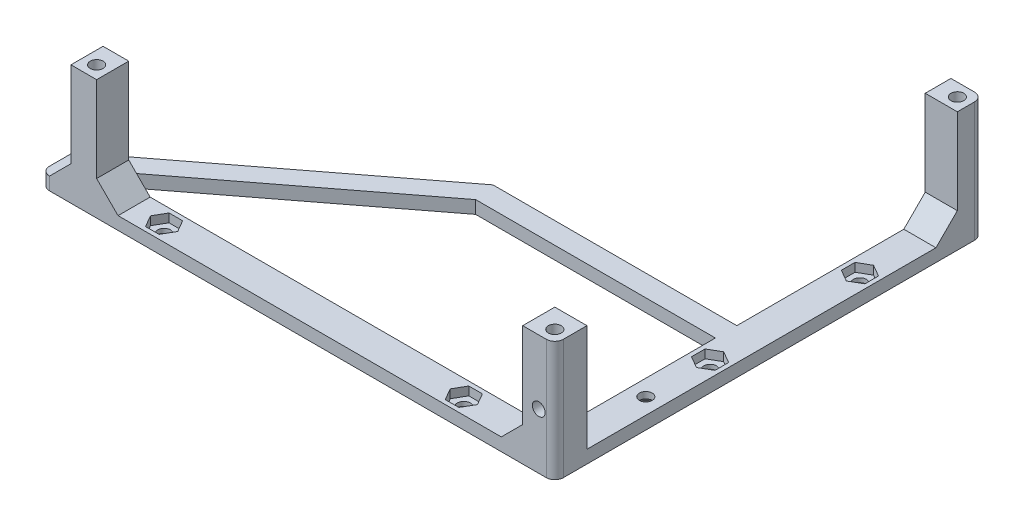
SolidWorks part; units mm, degrees
material "ABS"
ref_plane "Front Plane" through (0, 0, 0) normal (0, 0, 1) x (1, 0, 0)
ref_plane "Top Plane" through (0, 0, 0) normal (0, 1, 0) x (1, 0, 0)
ref_plane "Right Plane" through (0, 0, 0) normal (1, 0, 0) x (0, 0, -1)
sketch "Sketch1" plane through (0, 0, 0) normal (0, 1, 0) x (1, 0, 0)
  line L0 (40.0472, 27.5236) -> (44.5472, 27.5236)
  line L1 (47.5472, 24.5236) -> (47.5472, -70.4764)
  line L2 (45.5472, -72.4764) -> (-69.4528, -72.4764)
  line L3 (-72.4528, -69.4764) -> (-72.4528, -64.9764)
  line L4 (-72.4528, -64.9764) -> (40.0472, -64.9764)
  line L5 (40.0472, -64.9764) -> (40.0472, 27.5236)
  line L6 (-69.4528, -72.4764) -> (-70.4528, -72.4764)
  line L7 (-72.4528, -70.4764) -> (-72.4528, -69.4764)
  line L8 (47.5472, 24.5236) -> (47.5472, 25.5236)
  line L9 (45.5472, 27.5236) -> (44.5472, 27.5236)
  circle A3 centre (44.5472, 24.5236) radius 1.5
  circle A4 centre (44.5472, -69.4764) radius 1.5
  circle A5 centre (-62.4528, -69.4764) radius 1.5
  arc A6 (47.5472, -70.4764) -> (45.5472, -72.4764) centre (45.5472, -70.4764) cw
  arc A7 (47.5472, 25.5236) -> (45.5472, 27.5236) centre (45.5472, 25.5236) ccw
  arc A8 (-72.4528, -70.4764) -> (-70.4528, -72.4764) centre (-70.4528, -70.4764) ccw
  point P8 (-72.4528, -72.4764)
  point P11 (47.5472, -72.4764)
  point P14 (47.5472, 27.5236)
  point P22 (47.5472, 27.5236)
  point P26 (-72.4528, -72.4764)
  dimension "D4" = 2
  dimension "D7" = 10
  dimension "D8" = 3
  dimension "D9" = 2
  dimension "D1" = 7.5
  dimension "D2" = 100
  dimension "D3" = 120
  dimension "D5" = 3
  dimension "D6" = 3
extrude "Boss-Extrude1" add sketch "Sketch1" along normal blind 3
sketch "Sketch2" plane through (0, 3, 0) normal (0, 1, 0) x (1, 0, 0)
  line L0 (40.0472, -64.9764) -> (-72.4528, -64.9764) construction
  line L1 (40.0472, -64.9764) -> (47.5472, -64.9764)
  line L2 (40.0472, -64.9764) -> (40.0472, -72.4764)
  line L3 (40.0472, -72.4764) -> (45.5472, -72.4764)
  line L4 (47.5472, -64.9764) -> (47.5472, -70.4764)
  line L5 (-65.4528, -64.9764) -> (-59.4528, -64.9764)
  line L6 (-65.4528, -64.9764) -> (-65.4528, -72.4764)
  line L7 (-65.4528, -72.4764) -> (-59.4528, -72.4764)
  line L8 (-59.4528, -64.9764) -> (-59.4528, -72.4764)
  line L9 (40.0472, 27.5236) -> (40.0472, -64.9764) construction
  line L10 (40.0472, 21.5236) -> (47.5472, 21.5236)
  line L11 (40.0472, 21.5236) -> (40.0472, 27.5236)
  line L12 (40.0472, 27.5236) -> (45.5472, 27.5236)
  line L13 (47.5472, 21.5236) -> (47.5472, 25.5236)
  line L14 (-70.4528, -72.4764) -> (45.5472, -72.4764) construction
  line L15 (-62.4528, -64.9764) -> (-62.4528, -72.4764) construction
  line L16 (-63.9528, -69.4764) -> (-60.9528, -69.4764) construction
  line L17 (47.5472, -70.4764) -> (47.5472, 25.5236) construction
  line L18 (45.5472, 27.5236) -> (40.0472, 27.5236) construction
  circle A1 centre (-62.4528, -69.4764) radius 1.5 construction
  arc A2 (45.5472, -72.4764) -> (47.5472, -70.4764) centre (45.5472, -70.4764) ccw
  arc A3 (45.5472, 27.5236) -> (47.5472, 25.5236) centre (45.5472, 25.5236) cw
  arc A4 (45.5472, -72.4764) -> (47.5472, -70.4764) centre (45.5472, -70.4764) ccw construction
  arc A6 (47.5472, 25.5236) -> (45.5472, 27.5236) centre (45.5472, 25.5236) ccw construction
  point P26 (-62.4528, -69.4764)
  point P35 (47.5472, 27.5236)
  dimension "D1" = 6
  dimension "D3" = 6
extrude "Boss-Extrude2" add sketch "Sketch2" along normal blind 25
chamfer "Chamfer3" distance 5 angle 45 1 edges at (43.7972, 3, -21.5236)
chamfer "Chamfer6" distance 5 angle 45 1 edges at (40.0472, 3, 68.7264)
chamfer "Chamfer8" distance 5 angle 45 2 edges at (-59.4528, 3, 68.7264) (-65.4528, 3, 68.7264)
sketch "Sketch3" plane through (0, 0, 0) normal (0, -1, 0) x (-1, 0, 0)
  circle A0 centre (62.4528, -69.4764) radius 1.5
  circle A1 centre (-44.5472, -69.4764) radius 1.5
  circle A2 centre (-44.5472, 24.5236) radius 1.5
extrude "Cut-Extrude1" cut sketch "Sketch3" against normal through all
sketch "Sketch4" plane through (0, 0, 0) normal (0, -1, 0) x (-1, 0, 0)
  line L0 (-40.0472, -22.4764) -> (16.9006, -22.4764)
  line L1 (-40.0472, 16.5236) -> (-40.0472, -64.9764) construction
  line L2 (16.9006, -22.4764) -> (72.4528, -64.9764)
  line L3 (72.4528, -64.9764) -> (64.9528, -64.9764)
  line L4 (70.4528, -64.9764) -> (65.4528, -64.9764) construction
  line L5 (64.9528, -64.9764) -> (15.9361, -27.4764)
  line L6 (15.9361, -27.4764) -> (-40.0472, -27.4764)
  line L7 (-40.0472, -27.4764) -> (-40.0472, -22.4764)
  line L8 (54.4528, -72.4764) -> (-35.0472, -72.4764) construction
  dimension "D1" = 5
  dimension "D2" = 7.5
  dimension "D3" = 45
extrude "Boss-Extrude3" add sketch "Sketch4" against normal blind 3
sketch "Sketch5" plane through (0, 3, 0) normal (0, 1, 0) x (1, 0, 0)
  line L0 (-72.4528, -64.9764) -> (-72.4528, -70.4764) construction
  line L1 (-44.2774, -68.7264) -> (-45.8651, -65.9764)
  line L2 (-45.8651, -65.9764) -> (-49.0405, -65.9764)
  line L3 (-49.0405, -65.9764) -> (-50.6283, -68.7264)
  line L4 (-50.6283, -68.7264) -> (-49.0405, -71.4764)
  line L5 (-49.0405, -71.4764) -> (-45.8651, -71.4764)
  line L6 (-45.8651, -71.4764) -> (-44.2774, -68.7264)
  line L7 (-54.4528, -68.7264) -> (35.0472, -68.7264) construction
  line L8 (-54.4528, -64.9764) -> (-54.4528, -72.4764) construction
  line L9 (35.0472, -72.4764) -> (35.0472, -64.9764) construction
  line L10 (-54.4528, -72.4764) -> (35.0472, -72.4764) construction
  line L11 (47.5472, -70.4764) -> (47.5472, -64.9764) construction
  line L12 (25.7226, -68.7264) -> (24.1349, -65.9764)
  line L13 (24.1349, -65.9764) -> (20.9595, -65.9764)
  line L14 (20.9595, -65.9764) -> (19.3717, -68.7264)
  line L15 (19.3717, -68.7264) -> (20.9595, -71.4764)
  line L16 (20.9595, -71.4764) -> (24.1349, -71.4764)
  line L17 (24.1349, -71.4764) -> (25.7226, -68.7264)
  line L18 (43.7972, -64.9764) -> (43.7972, 16.5236) construction
  line L19 (43.7972, -0.6518) -> (46.5472, 0.9359)
  line L20 (46.5472, 0.9359) -> (46.5472, 4.1113)
  line L21 (46.5472, 4.1113) -> (43.7972, 5.699)
  line L22 (43.7972, 5.699) -> (41.0472, 4.1113)
  line L23 (41.0472, 4.1113) -> (41.0472, 0.9359)
  line L24 (41.0472, 0.9359) -> (43.7972, -0.6518)
  line L25 (43.7972, -35.6518) -> (46.5472, -34.0641)
  line L26 (46.5472, -34.0641) -> (46.5472, -30.8887)
  line L27 (46.5472, -30.8887) -> (43.7972, -29.301)
  line L28 (43.7972, -29.301) -> (41.0472, -30.8887)
  line L29 (41.0472, -30.8887) -> (41.0472, -34.0641)
  line L30 (41.0472, -34.0641) -> (43.7972, -35.6518)
  line L31 (47.5472, -64.9764) -> (40.0472, -64.9764) construction
  line L32 (47.5472, 16.5236) -> (40.0472, 16.5236) construction
  line L33 (40.0472, -72.4764) -> (45.5472, -72.4764) construction
  line L34 (45.5472, 27.5236) -> (40.0472, 27.5236) construction
  line L35 (47.5472, -64.9764) -> (47.5472, 16.5236) construction
  circle A0 centre (-47.4528, -68.7264) radius 2.75 construction
  circle A1 centre (22.5472, -68.7264) radius 2.75 construction
  circle A2 centre (43.7972, 2.5236) radius 2.75 construction
  circle A3 centre (43.7972, -32.4764) radius 2.75 construction
  dimension "D1" = 5.5
  dimension "D2" = 25
  dimension "D3" = 25
  dimension "D4" = 40
  dimension "D5" = 25
extrude "Cut-Extrude2" cut sketch "Sketch5" against normal blind 2
sketch "Sketch6" plane through (0, 1, 0) normal (0, 1, 0) x (1, 0, 0)
  line L0 (-54.4528, -68.7264) -> (35.0472, -68.7264) construction
  line L1 (-54.4528, -64.9764) -> (-54.4528, -72.4764) construction
  line L2 (35.0472, -72.4764) -> (35.0472, -64.9764) construction
  line L3 (-47.4528, -65.9764) -> (-47.4528, -71.4764) construction
  line L4 (-45.8651, -65.9764) -> (-49.0405, -65.9764) construction
  line L5 (-49.0405, -71.4764) -> (-45.8651, -71.4764) construction
  line L6 (22.5472, -65.9764) -> (22.5472, -71.4764) construction
  line L7 (24.1349, -65.9764) -> (20.9595, -65.9764) construction
  line L8 (20.9595, -71.4764) -> (24.1349, -71.4764) construction
  line L9 (41.0472, -32.4764) -> (46.5472, -32.4764) construction
  line L10 (41.0472, -30.8887) -> (41.0472, -34.0641) construction
  line L11 (46.5472, -34.0641) -> (46.5472, -30.8887) construction
  line L12 (43.7972, -64.9764) -> (43.7972, 16.5236) construction
  line L13 (47.5472, -64.9764) -> (40.0472, -64.9764) construction
  line L14 (47.5472, 16.5236) -> (40.0472, 16.5236) construction
  line L15 (41.0472, 2.5236) -> (46.5472, 2.5236) construction
  line L16 (41.0472, 4.1113) -> (41.0472, 0.9359) construction
  line L17 (46.5472, 0.9359) -> (46.5472, 4.1113) construction
  circle A0 centre (43.7972, 2.5236) radius 1.5
  circle A1 centre (43.7972, -32.4764) radius 1.5
  circle A2 centre (22.5472, -68.7264) radius 1.5
  circle A3 centre (-47.4528, -68.7264) radius 1.5
  circle A4 centre (43.7972, -47.4764) radius 1.5
  dimension "D1" = 3
  dimension "D2" = 3
  dimension "D3" = 17.5
extrude "Cut-Extrude3" cut sketch "Sketch6" against normal through all and the other way blind 10
sketch "Sketch9" plane through (0, 0, 72.4764) normal (0, 0, 1) x (1, 0, 0)
  line L0 (-54.4528, 3) -> (35.0472, 3) construction
  line L1 (47.5472, 28) -> (47.5472, 0) construction
  circle A0 centre (43.7972, 13) radius 1.4933
  dimension "D1" = 10
  dimension "D2" = 3.75
extrude "Cut-Extrude4" cut sketch "Sketch9" against normal blind 10
chamfer "Chamfer9" distance 1.5 angle 45 1 edges at (43.7972, 0, 48.9764)
